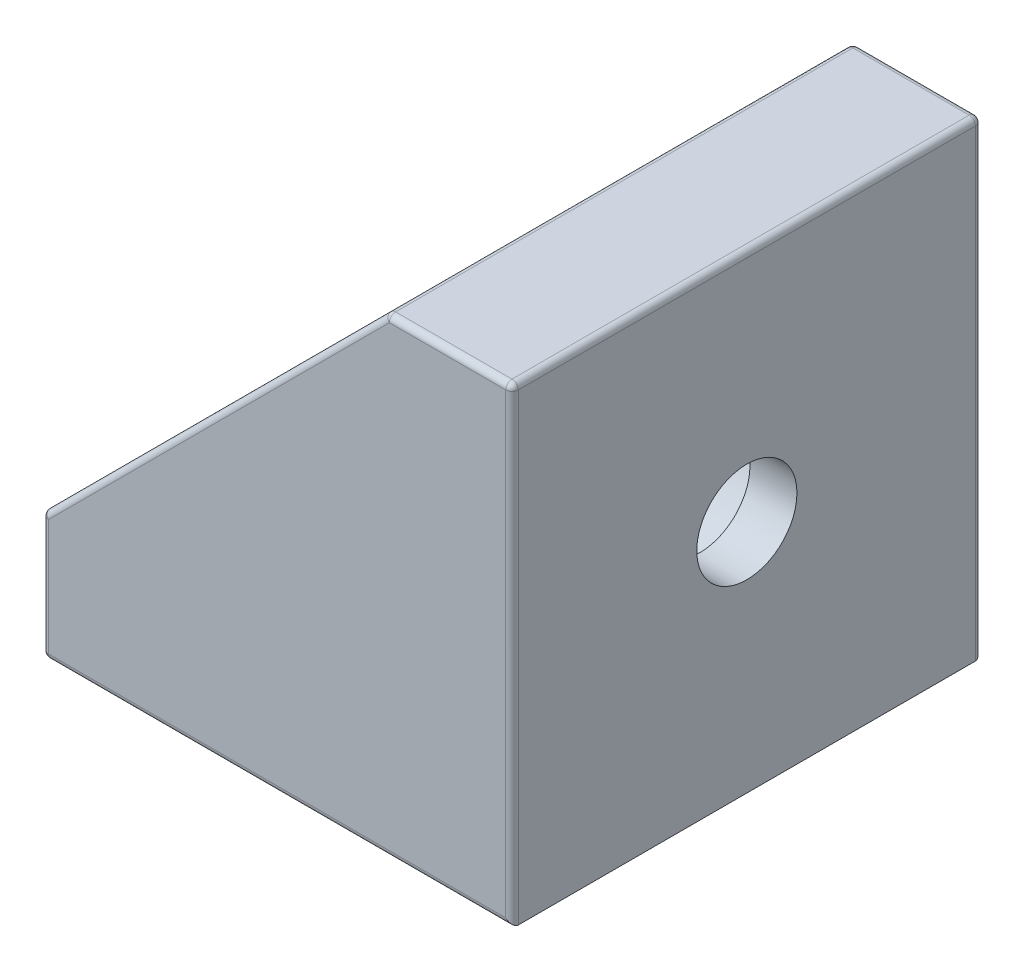
SolidWorks part; units mm, degrees
ref_plane "Front Plane" through (0, 0, 0) normal (0, 0, 1) x (1, 0, 0)
ref_plane "Top Plane" through (0, 0, 0) normal (0, 1, 0) x (1, 0, 0)
ref_plane "Right Plane" through (0, 0, 0) normal (1, 0, 0) x (0, 0, -1)
sketch "Sketch2" plane through (0, 0, 0) normal (0, 0, 1) x (1, 0, 0)
  line L0 (0, 0) -> (30, 0)
  line L1 (30, 0) -> (30, 30)
  line L2 (30, 30) -> (22, 30)
  line L3 (22, 30) -> (0, 8)
  line L4 (0, 8) -> (0, 0)
  dimension "D1" = 30
  dimension "D2" = 30
  dimension "D3" = 8
  dimension "D4" = 8
extrude "Boss-Extrude1" add sketch "Sketch2" along normal blind 30
sketch "Sketch3" plane through (30, 0, 0) normal (1, 0, 0) x (0, 0, -1)
  line L0 (-15, 30) -> (-15, 15) construction
  line L1 (-30, 30) -> (0, 30) construction
  circle A1 centre (-15, 15) radius 3.2
  dimension "D1" = 15
  dimension "D2" = 6.4
extrude "Cut-Extrude8" cut sketch "Sketch3" against normal blind 33
sketch "Sketch5" plane through (0, 0, 0) normal (0, -1, 0) x (1, 0, 0)
  line L0 (0, 15) -> (15, 15) construction
  line L1 (0, 30) -> (0, 0) construction
  circle A0 centre (15, 15) radius 3.2
  dimension "D2" = 6.4
  dimension "D1" = 15
extrude "Cut-Extrude5" cut sketch "Sketch5" against normal blind 32
sketch "Sketch7" plane through (0, 30, 0) normal (0, 1, 0) x (1, 0, 0)
  circle A0 centre (15, -15) radius 6
  circle A1 centre (15, -15) radius 3.2 construction
  circle A2 centre (15, -15) radius 3.2
  dimension "D1" = 12
sketch "Sketch8" plane through (0, 0, 0) normal (-1, 0, 0) x (0, 0, 1)
  circle A0 centre (15, 15) radius 6
  circle A1 centre (15, 15) radius 3.2 construction
  circle A2 centre (15, 15) radius 3.2
  point P5 (0, 0)
  dimension "D1" = 12
extrude "Cut-Extrude9" cut sketch "Sketch8" against normal blind 27
extrude "Cut-Extrude10" cut sketch "Sketch7" against normal blind 27
fillet "Fillet6" radius 0.4 16 edges at (30, 30, 15) (26, 30, 30) (30, 15, 30) (15, 0, 30) (0, 4, 30) (0, 0, 15) (15, 0, 0) (30, 15, 0) (26, 30, 0) (0, 4, 0) (22, 30, 15) (11, 19, 30) (0, 8, 15) (11, 19, 0) (1, 9, 15) (21, 29, 15)
